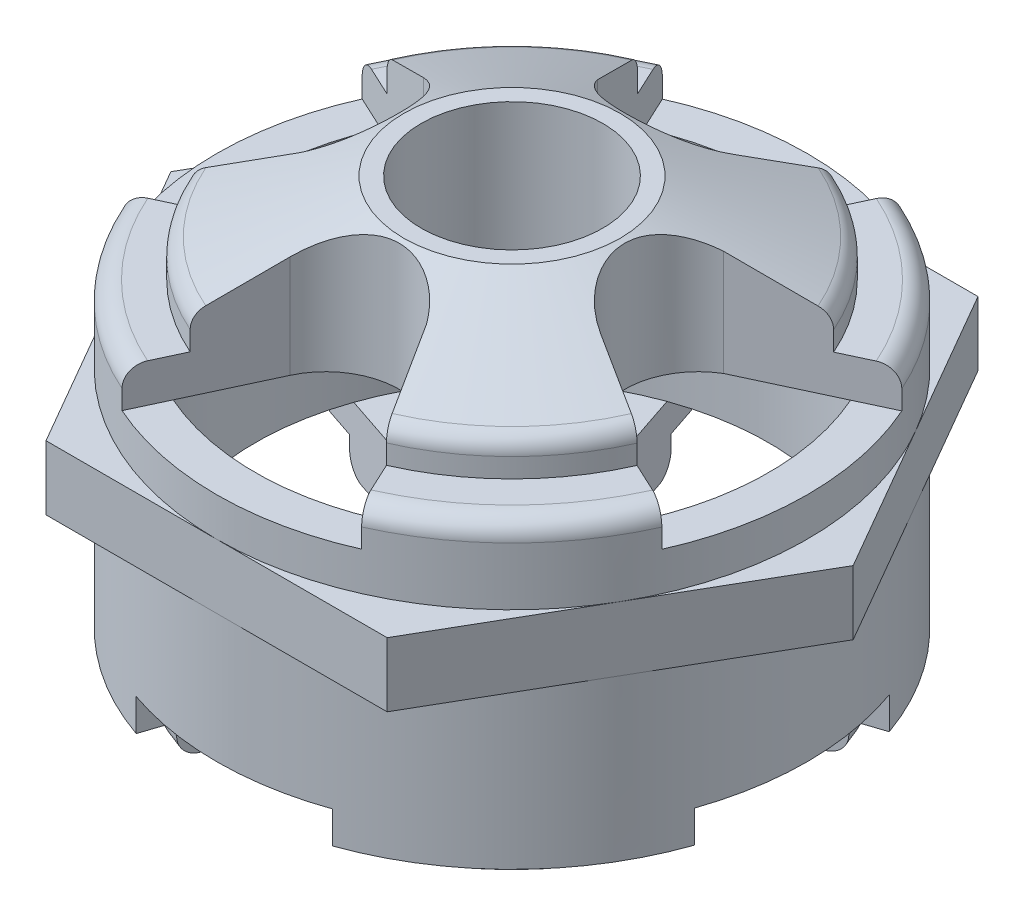
SolidWorks part; units mm, degrees
material "2024-O"
ref_plane "Front Plane" through (0, 0, 0) normal (0, 0, 1) x (1, 0, 0)
ref_plane "Top Plane" through (0, 0, 0) normal (0, 1, 0) x (1, 0, 0)
ref_plane "Right Plane" through (0, 0, 0) normal (1, 0, 0) x (0, 0, -1)
sketch "Sketch1" plane through (0, 0, 0) normal (0, 0, 1) x (1, 0, 0)
  line L0 (0, -1000) -> (0, 49000) construction
  line L1 (0, 8.25) -> (0, -8.25)
  line L2 (-11.5, 8.25) -> (11.5, 8.25) construction
  line L3 (-11.5, 8.25) -> (-11.5, -8.25) construction
  line L4 (-11.5, -8.25) -> (11.5, -8.25) construction
  line L5 (11.5, 8.25) -> (11.5, -8.25) construction
  line L6 (-11.5, 8.25) -> (11.5, -8.25) construction
  line L7 (-11.5, -8.25) -> (11.5, 8.25) construction
  line L8 (0, -8.25) -> (-9.5042, -8.25)
  line L9 (-10.2542, -7.5) -> (-10.2542, -7)
  line L10 (-10.2542, -7) -> (-11.5, -7)
  line L11 (-11.5, -7) -> (-11.5, 4)
  line L12 (-10.75, 4.75) -> (-9.5042, 4.75)
  line L13 (-9.5042, 4.75) -> (-9.5042, 5.5039)
  line L14 (-9.0477, 6.1941) -> (-4.2127, 8.25)
  line L15 (-4.2127, 8.25) -> (0, 8.25)
  arc A0 (-11.5, 4) -> (-10.75, 4.75) centre (-10.75, 4) cw
  arc A1 (-9.5042, 5.5039) -> (-9.0477, 6.1941) centre (-8.7542, 5.5039) cw
  arc A2 (-9.5042, -8.25) -> (-10.2542, -7.5) centre (-9.5042, -7.5) cw
  point P1 (0, 0)
  point P19 (-11.5, 4.75)
  point P22 (-9.5042, 6)
  point P25 (-10.2542, -8.25)
  dimension "D7" = 0.75
  dimension "D1" = 16.5
  dimension "D2" = 23
  dimension "D3" = 1.25
  dimension "D6" = 5.75
  dimension "D4" = 11.75
revolve "Revolve1" add sketch "Sketch1" angle 360 about L0 other way angle 360
sketch "Sketch2" plane through (0, 8.25, 0) normal (0, 1, 0) x (1, 0, 0)
  line L0 (0, -1000) -> (0, 49000) construction
  line L1 (-4.6607, 10.5132) -> (-2.4557, 5.7846)
  line L2 (2.5917, 6.0415) -> (4.6742, 10.5072)
  line L3 (10.5132, 4.6607) -> (5.7846, 2.4557)
  line L4 (6.0415, -2.5917) -> (10.5072, -4.6742)
  line L5 (4.6607, -10.5132) -> (2.4557, -5.7846)
  line L6 (-2.5917, -6.0415) -> (-4.6742, -10.5072)
  line L7 (-10.5132, -4.6607) -> (-5.7846, -2.4557)
  line L8 (-6.0415, 2.5917) -> (-10.5072, 4.6742)
  line L10 (-2.5, 2.5) -> (2.5, 2.5)
  line L11 (-2.5, 2.5) -> (-2.5, -2.5)
  line L12 (-2.5, -2.5) -> (2.5, -2.5)
  line L13 (2.5, 2.5) -> (2.5, -2.5)
  line L14 (-2.5, 2.5) -> (2.5, -2.5) construction
  line L15 (-2.5, -2.5) -> (2.5, 2.5) construction
  circle A0 centre (0, 0) radius 11.5 construction
  arc A1 (-10.5072, 4.6742) -> (-10.5132, -4.6607) centre (0, 0) ccw
  circle A2 centre (0, 0) radius 10
  arc A3 (-2.4557, 5.7846) -> (2.5917, 6.0415) centre (0, 7.25) ccw
  arc A4 (5.7846, 2.4557) -> (6.0415, -2.5917) centre (7.25, 0) ccw
  arc A5 (2.4557, -5.7846) -> (-2.5917, -6.0415) centre (0, -7.25) ccw
  arc A6 (-5.7846, -2.4557) -> (-6.0415, 2.5917) centre (-7.25, 0) ccw
  arc A7 (-4.6742, -10.5072) -> (4.6607, -10.5132) centre (0, 0) ccw
  arc A8 (10.5072, -4.6742) -> (10.5132, 4.6607) centre (0, 0) ccw
  arc A9 (4.6742, 10.5072) -> (-4.6607, 10.5132) centre (0, 0) ccw
  circle A10 centre (0, 0) radius 3.5355
  point P29 (0, 0)
  dimension "D1" = 1.5
  dimension "D4" = 7.25
  dimension "D2" = 25
  dimension "D3" = 25
  dimension "D6" = 5
  dimension "D5" = 4
extrude "Cut-Extrude1" cut sketch "Sketch2" against normal blind 5 contours L8 A1 L7 A6 | L1 A3 L2 A9 | L4 A8 L3 A4 | L6 A7 L5 A5
sketch "Sketch4" plane through (0, -8.25, 0) normal (0, -1, 0) x (1, 0, 0)
  line L0 (0, -999.962) -> (0, 49000.038) construction
  line L1 (10.8675, 3.7612) -> (5.8239, 2.0737)
  line L2 (-3.7612, 10.8675) -> (-2.0737, 5.8239)
  line L3 (2.3867, 6.4514) -> (3.8534, 10.8352)
  line L4 (6.4514, -2.3867) -> (10.8352, -3.8534)
  line L5 (3.7612, -10.8675) -> (2.0737, -5.8239)
  line L6 (-2.3867, -6.4514) -> (-3.8534, -10.8352)
  line L7 (-10.8675, -3.7612) -> (-5.8239, -2.0737)
  line L8 (-6.4514, 2.3867) -> (-10.8352, 3.8534)
  arc A0 (4.6607, 10.5132) -> (-4.6742, 10.5072) centre (0, 0) ccw construction
  arc A1 (-2.0737, 5.8239) -> (2.3867, 6.4514) centre (0, 7.25) ccw
  arc A2 (3.8534, 10.8352) -> (-3.7612, 10.8675) centre (0, 0) ccw
  arc A3 (5.8239, 2.0737) -> (6.4514, -2.3867) centre (7.25, 0) ccw
  arc A4 (10.8352, -3.8534) -> (10.8675, 3.7612) centre (0, 0) ccw
  arc A5 (2.0737, -5.8239) -> (-2.3867, -6.4514) centre (0, -7.25) ccw
  arc A6 (-3.8534, -10.8352) -> (3.7612, -10.8675) centre (0, 0) ccw
  arc A7 (-5.8239, -2.0737) -> (-6.4514, 2.3867) centre (-7.25, 0) ccw
  arc A8 (-10.8352, 3.8534) -> (-10.8675, -3.7612) centre (0, 0) ccw
  point P30 (0, 0)
  dimension "D3" = 4
  dimension "D1" = 18.5
  dimension "D2" = 18.5
extrude "Cut-Extrude2" cut sketch "Sketch4" against normal blind 2.5 contours L8 A8 L7 A7 | L2 A1 L3 A2 | L1 A3 L4 A4 | L5 A5 L6 A6
extrude "Cut-Extrude3" cut sketch "Sketch2<3>" against normal up to surface (14 mm away) from offset 5 contours A2 up to face at (-0.1505, -5.75, -8.3117) offset against normal yes
sketch "Sketch2<3>" plane through (0, 8.25, 0) normal (0, 1, 0) x (1, 0, 0) same geometry as "Sketch2"
extrude "Cut-Extrude4" cut sketch "Sketch2<4>" against normal through all contours A10
sketch "Sketch2<4>" plane through (0, 8.25, 0) normal (0, 1, 0) x (1, 0, 0) same geometry as "Sketch2"
sketch "Sketch5" plane through (0, 3.25, 0) normal (0, 1, 0) x (1, 0, 0)
  line L1 (-6.6395, 11.5) -> (-13.2791, 0)
  line L2 (-13.2791, 0) -> (-6.6395, -11.5)
  line L3 (-6.6395, -11.5) -> (6.6395, -11.5)
  line L4 (6.6395, -11.5) -> (13.2791, 0)
  line L5 (13.2791, 0) -> (6.6395, 11.5)
  line L6 (6.6395, 11.5) -> (-6.6395, 11.5)
  arc A0 (-10.5072, 4.6742) -> (-10.5132, -4.6607) centre (0, 0) ccw construction
  arc A1 (-10.5072, 4.6742) -> (-10.5132, -4.6607) centre (0, 0) ccw
  circle A2 centre (0, 0) radius 11.5 construction
  circle A3 centre (0, 0) radius 10
  arc A5 (-9.1475, 4.0401) -> (-9.1535, -4.0266) centre (0, 0) ccw construction
  line M5 (-9.1475, 4.0401) -> (-10.5072, 4.6742)
  arc M6 (-10.5072, 4.6742) -> (-10.5132, -4.6607) centre (0, 0) ccw
  line M7 (-10.5132, -4.6607) -> (-9.1535, -4.0266)
  dimension "D1" = 11.5
extrude "Boss-Extrude1" add sketch "Sketch5" against normal blind 2.5 from offset 1.5 contours L5 L6 L1 L2 L3 L4 A3 M7 M6 M5 region at (0, 3.25, -11.1487) offset against normal yes
equation "\"D4@Sketch1\"=\"D1@Sketch1\"-4.75"
